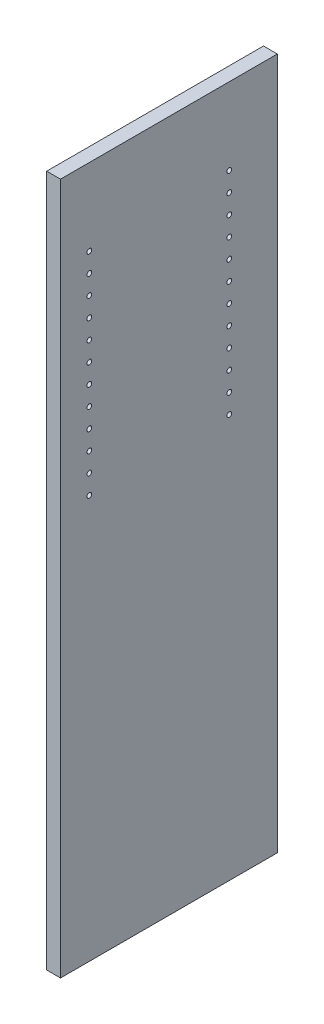
SolidWorks part; units mm, degrees
material "Cedar"
ref_plane "Front Plane" through (0, 0, 0) normal (0, 0, 1) x (1, 0, 0)
ref_plane "Top Plane" through (0, 0, 0) normal (0, 1, 0) x (1, 0, 0)
ref_plane "Right Plane" through (0, 0, 0) normal (1, 0, 0) x (0, 0, -1)
sketch "Sketch1" plane through (0, 0, 0) normal (1, 0, 0) x (0, 0, -1)
  line L1 (-143.2719, -457.2) -> (143.2719, -457.2)
  line L2 (-143.2719, -457.2) -> (-143.2719, 457.2)
  line L3 (-143.2719, 457.2) -> (143.2719, 457.2)
  line L4 (143.2719, -457.2) -> (143.2719, 457.2)
  line L5 (-143.2719, -457.2) -> (143.2719, 457.2) construction
  line L6 (-143.2719, 457.2) -> (143.2719, -457.2) construction
  point P0 (0, 0)
  dimension "D1" = 286.5437
  dimension "D2" = 914.4
extrude "Boss-Extrude1" add sketch "Sketch1" along normal blind 18.2562
sketch "Sketch3" plane through (18.2562, 0, 0) normal (1, 0, 0) x (0, 0, -1)
  line L0 (-105.1719, 457.2) -> (-105.1719, -457.2) construction
  line L1 (143.2719, 457.2) -> (-143.2719, 457.2) construction
  line L2 (-143.2719, -457.2) -> (143.2719, -457.2) construction
  line L3 (-12.7, 457.2) -> (-12.7, -457.2) construction
  line L4 (-143.2719, 457.2) -> (-143.2719, -457.2) construction
  line L5 (0, 0) -> (-12.7, 0) construction
  circle A0 centre (-105.1719, 355.6) radius 3.175
  circle A1 centre (-105.1719, 330.2) radius 3.175
  circle A2 centre (-105.1719, 304.8) radius 3.175
  circle A3 centre (-105.1719, 279.4) radius 3.175
  circle A4 centre (-105.1719, 254) radius 3.175
  circle A5 centre (-105.1719, 228.6) radius 3.175
  circle A6 centre (-105.1719, 203.2) radius 3.175
  circle A7 centre (-105.1719, 177.8) radius 3.175
  circle A8 centre (-105.1719, 152.4) radius 3.175
  circle A9 centre (-105.1719, 127) radius 3.175
  circle A10 centre (-105.1719, 101.6) radius 3.175
  circle A11 centre (-105.1719, 76.2) radius 3.175
  circle A12 centre (79.7719, 76.2) radius 3.175
  circle A13 centre (79.7719, 101.6) radius 3.175
  circle A14 centre (79.7719, 127) radius 3.175
  circle A15 centre (79.7719, 152.4) radius 3.175
  circle A16 centre (79.7719, 177.8) radius 3.175
  circle A17 centre (79.7719, 203.2) radius 3.175
  circle A18 centre (79.7719, 228.6) radius 3.175
  circle A19 centre (79.7719, 254) radius 3.175
  circle A20 centre (79.7719, 279.4) radius 3.175
  circle A21 centre (79.7719, 304.8) radius 3.175
  circle A22 centre (79.7719, 330.2) radius 3.175
  circle A23 centre (79.7719, 355.6) radius 3.175
  dimension "D1" = 6.35
  dimension "D2" = 38.1
  dimension "D3" = 101.6
  dimension "D5" = 25.4
  dimension "D6" = 12.7
  dimension "D4" = 12
extrude "Cut-Extrude1" cut sketch "Sketch3" against normal blind 9.525
